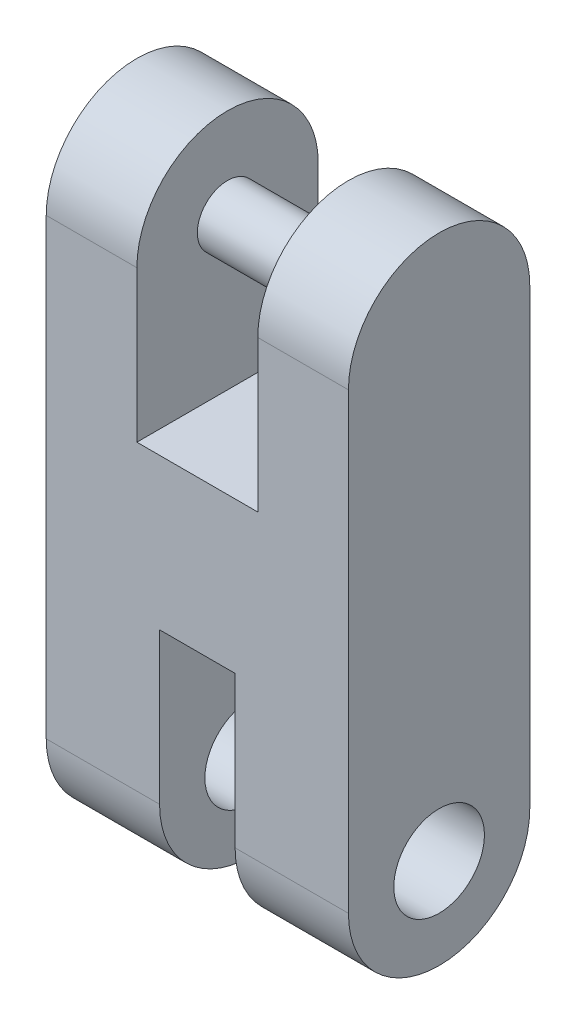
SolidWorks part; units mm, degrees
ref_plane "Alzado" through (0, 0, 0) normal (0, 0, 1) x (1, 0, 0)
ref_plane "Planta" through (0, 0, 0) normal (0, 1, 0) x (1, 0, 0)
ref_plane "Vista lateral" through (0, 0, 0) normal (1, 0, 0) x (0, 0, -1)
sketch "Croquis1" plane through (0, 0, 0) normal (0, 0, 1) x (1, 0, 0)
  line L0 (-7, 21) -> (-7, 13)
  line L1 (0, 0) -> (-3.75, 0)
  line L2 (0, 0) -> (0, 21)
  line L3 (0, 21) -> (-3, 21)
  line L4 (-10, 0) -> (-10, 21)
  line L5 (-7, 13) -> (-3, 13)
  line L6 (-3, 13) -> (-3, 21)
  line L7 (-6.25, 0) -> (-6.25, 8)
  line L8 (-6.25, 8) -> (-3.75, 8)
  line L9 (-3.75, 8) -> (-3.75, 0)
  line L10 (-7, 21) -> (-10, 21)
  line L11 (-6.25, 0) -> (-10, 0)
  line L12 (-10, 21) -> (-10, 24.8643) construction
  line L13 (-10, 24.8643) -> (0, 24.8643) construction
  line L14 (0, 24.8643) -> (0, 21) construction
  line L15 (-10, 0) -> (-10, -2.8007) construction
  line L16 (-10, -2.8007) -> (0, -2.8007) construction
  line L17 (0, -2.8007) -> (0, 0) construction
  line L18 (-5, 24.8643) -> (-5, -2.8007) construction
  dimension "D1" = 3
  dimension "D2" = 3
  dimension "D3" = 8
  dimension "D4" = 8
  dimension "D5" = 5
  dimension "D6" = 2.5
  dimension "D7" = 4
  dimension "D8" = 1.25
extrude "Saliente-Extruir1" add sketch "Croquis1" along normal blind 6
fillet "Redondeo1" 2 edges at (-1.875, 0, 6) (-1.875, 0, 0) type full round first side face at (-5, 10.5, 6) second side face at (-5, 10.5, 0) middle face at (-1.875, 0, 3)
fillet "Redondeo2" 2 edges at (-1.5, 21, 6) (-1.5, 21, 0) type full round first side face at (-5, 11, 6) second side face at (-5, 11, 0) middle face at (-1.5, 21, 3)
fillet "Redondeo3" 2 edges at (-8.5, 21, 0) (-8.5, 21, 6) type full round first side face at (-5, 10.5, 0) second side face at (-5, 10.5, 6) middle face at (-8.5, 21, 3)
fillet "Redondeo4" 2 edges at (-8.125, 0, 0) (-8.125, 0, 6) type full round first side face at (-5, 10, 0) second side face at (-5, 10, 6) middle face at (-8.125, 0, 3)
sketch "Croquis2" plane through (0, 0, 0) normal (1, 0, 0) x (0, 0, -1)
  line L0 (-3, 21) -> (-3, 0) construction
  line L1 (-6, 3) -> (0, 3) construction
  line L2 (-6, 18) -> (0, 18) construction
  circle A0 centre (-3, 3) radius 1.5
  arc A1 (0, 18) -> (-6, 18) centre (-3, 18) ccw construction
  arc A2 (-6, 3) -> (0, 3) centre (-3, 3) ccw construction
  circle A3 centre (-3, 18) radius 1
  dimension "D1" = 3
  dimension "D2" = 2
extrude "Cortar-Extruir1" cut sketch "Croquis2" against normal up to surface (10 mm away) up to face at (-10, 10.5, 3)
sketch "Croquis6" plane through (-10, 0, 0) normal (-1, 0, 0) x (0, 0, 1)
  line L0 (0, 18) -> (6, 18) construction
  arc A0 (6, 18) -> (0, 18) centre (3, 18) ccw construction
  circle A1 centre (3, 18) radius 1
extrude "Saliente-Extruir3" add sketch "Croquis6" against normal blind 10
